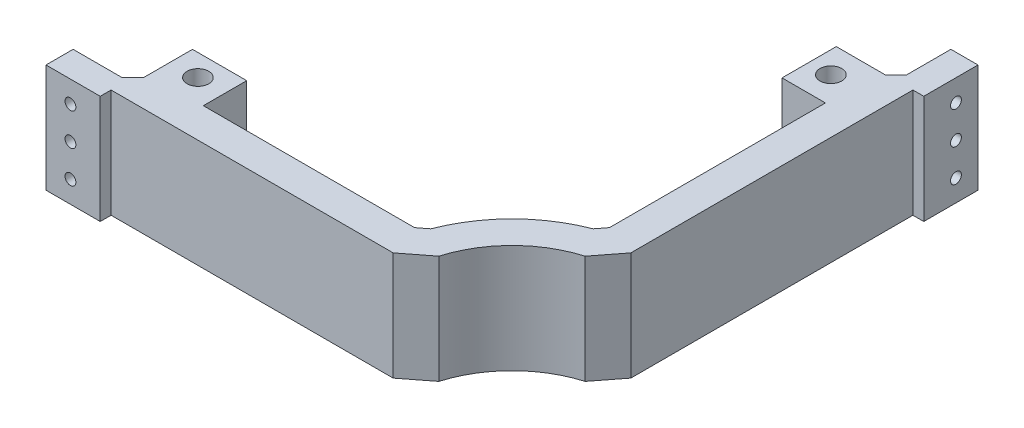
SolidWorks part; units mm, degrees
ref_plane "Front Plane" through (0, 0, 0) normal (0, 0, 1) x (1, 0, 0)
ref_plane "Top Plane" through (0, 0, 0) normal (0, 1, 0) x (1, 0, 0)
ref_plane "Right Plane" through (0, 0, 0) normal (1, 0, 0) x (0, 0, -1)
sketch "Sketch2" plane through (0, 0, 0) normal (0, 1, 0) x (1, 0, 0)
  line L0 (47.6057, -102.775) -> (59.4531, -93.5751)
  line L1 (87.3943, 56.695) -> (67.3943, 56.695)
  line L2 (102.3943, -47.9864) -> (93.1944, -59.8338)
  line L3 (107.3943, 107.0136) -> (107.3943, 82.0136)
  line L4 (-54.8742, -87.775) -> (-54.8742, -67.775)
  line L5 (-54.8742, -67.775) -> (-79.8742, -67.775)
  line L6 (-79.8742, -67.775) -> (-79.8742, -95.275)
  line L7 (-79.8742, -95.275) -> (-107.3943, -95.275)
  line L8 (-107.3943, -95.275) -> (-107.3943, -107.775)
  line L9 (-107.3943, -107.775) -> (-82.3943, -107.775)
  line L10 (-82.3943, -107.775) -> (-82.3943, -102.775)
  line L11 (107.3943, -107.775) -> (-5.1294, -107.775) construction
  line L12 (67.3943, 81.695) -> (67.3943, 56.695)
  line L13 (67.3943, 81.695) -> (94.8943, 81.695)
  line L14 (107.3943, 82.0136) -> (102.3943, 82.0136)
  line L15 (107.3943, -107.775) -> (107.3943, 82.0136) construction
  line L16 (94.8943, 81.695) -> (94.8943, 107.0136)
  line L17 (94.8943, 107.0136) -> (107.3943, 107.0136)
  line L18 (47.6057, -102.775) -> (-54.8742, -102.775)
  line L19 (102.3943, 56.695) -> (102.3943, -47.9864)
  line L20 (87.3943, 56.695) -> (87.3943, -42.8463)
  line L21 (87.3943, -42.8463) -> (84.0957, -47.0941)
  line L22 (42.4656, -87.775) -> (46.7134, -84.4764)
  line L23 (42.4656, -87.775) -> (-54.8742, -87.775)
  line L24 (-82.3943, -102.775) -> (-54.8742, -102.775)
  line L25 (102.3943, 82.0136) -> (102.3943, 56.695)
  arc A0 (93.1944, -59.8338) -> (59.4531, -93.5751) centre (107.3943, -107.775) ccw
  arc A1 (84.0957, -47.0941) -> (46.7134, -84.4764) centre (107.3943, -107.775) ccw
  arc A2 (107.3943, -57.775) -> (59.4531, -93.5751) centre (107.3943, -107.775) ccw
  point P0 (57.5862, -103.3993)
  point P3 (103.0186, -57.9669)
  dimension "D5" = 100
  dimension "D1" = 10
  dimension "D2" = 10
  dimension "D3" = 10
  dimension "D4" = 10
  dimension "D6" = 25
  dimension "D7" = 25
  dimension "D8" = 25
  dimension "D9" = 25
  dimension "D10" = 130
  dimension "D11" = 130
  dimension "D12" = 7.5
  dimension "D13" = 7.5
  dimension "D14" = 15
  dimension "D15" = 15
  dimension "D16" = 5
  dimension "D17" = 152.148
extrude "Boss-Extrude1" add sketch "Sketch2" along normal blind 50 contours L21 A1 L22 L23 L4 L5 L6 L7 L8 L9 L10 L24 L18 L0 A0 L2 L19 L25 L14 L3 L17 L16 L13 L12 L1 L20 region at (-3.6343, 0, 99.7375)
sketch "Sketch3" plane through (0, 50, 0) normal (0, 1, 0) x (1, 0, 0)
  line L0 (-54.8742, -77.775) -> (-79.8742, -77.775) construction
  line L1 (-54.8742, -87.775) -> (-54.8742, -67.775) construction
  line L2 (-79.8742, -67.775) -> (-79.8742, -95.275) construction
  line L3 (77.3943, 56.695) -> (77.3943, 81.695) construction
  line L4 (87.3943, 56.695) -> (67.3943, 56.695) construction
  line L5 (67.3943, 81.695) -> (94.8943, 81.695) construction
  circle A0 centre (77.3943, 69.195) radius 5
  circle A1 centre (-67.3742, -77.775) radius 5
  dimension "D1" = 10
  dimension "D2" = 10
extrude "Cut-Extrude1" cut sketch "Sketch3" against normal blind 50
chamfer "Chamfer1" distance 5 angle 45 1 edges at (94.8943, 25, -81.695)
chamfer "Chamfer2" distance 5 angle 45 1 edges at (-79.8742, 25, 95.275)
sketch "Sketch4" plane through (94.8943, 0, 0) normal (-1, 0, 0) x (0, 0, 1)
  line L0 (-107.0136, 25) -> (-86.695, 25)
  line L1 (-107.0136, 50) -> (-107.0136, 0) construction
  line L2 (-86.695, 0) -> (-86.695, 50) construction
  circle A0 centre (-96.8543, 25) radius 2.5
  circle A1 centre (-96.8543, 40) radius 2.5
  circle A2 centre (-96.8543, 10) radius 2.5
  dimension "D1" = 5
  dimension "D2" = 15
  dimension "D3" = 15
extrude "Cut-Extrude2" cut sketch "Sketch4" against normal blind 50 contours A2 | A0 | A1 region at (94.8943, 10, -96.8543)
sketch "Sketch5" plane through (0, 0, 95.275) normal (0, 0, -1) x (-1, 0, 0)
  line L0 (107.3943, 25) -> (84.8742, 25)
  line L1 (107.3943, 50) -> (107.3943, 0) construction
  line L2 (84.8742, 50) -> (84.8742, 0) construction
  circle A0 centre (96.1343, 25) radius 2.5
  circle A1 centre (96.1343, 40) radius 2.5
  circle A2 centre (96.1343, 10) radius 2.5
  dimension "D1" = 5
  dimension "D2" = 15
  dimension "D3" = 15
extrude "Cut-Extrude3" cut sketch "Sketch5" against normal blind 50 contours A1 | A2 | A0 region at (-96.1343, 40, 95.275) region at (-96.1343, 10, 95.275)
